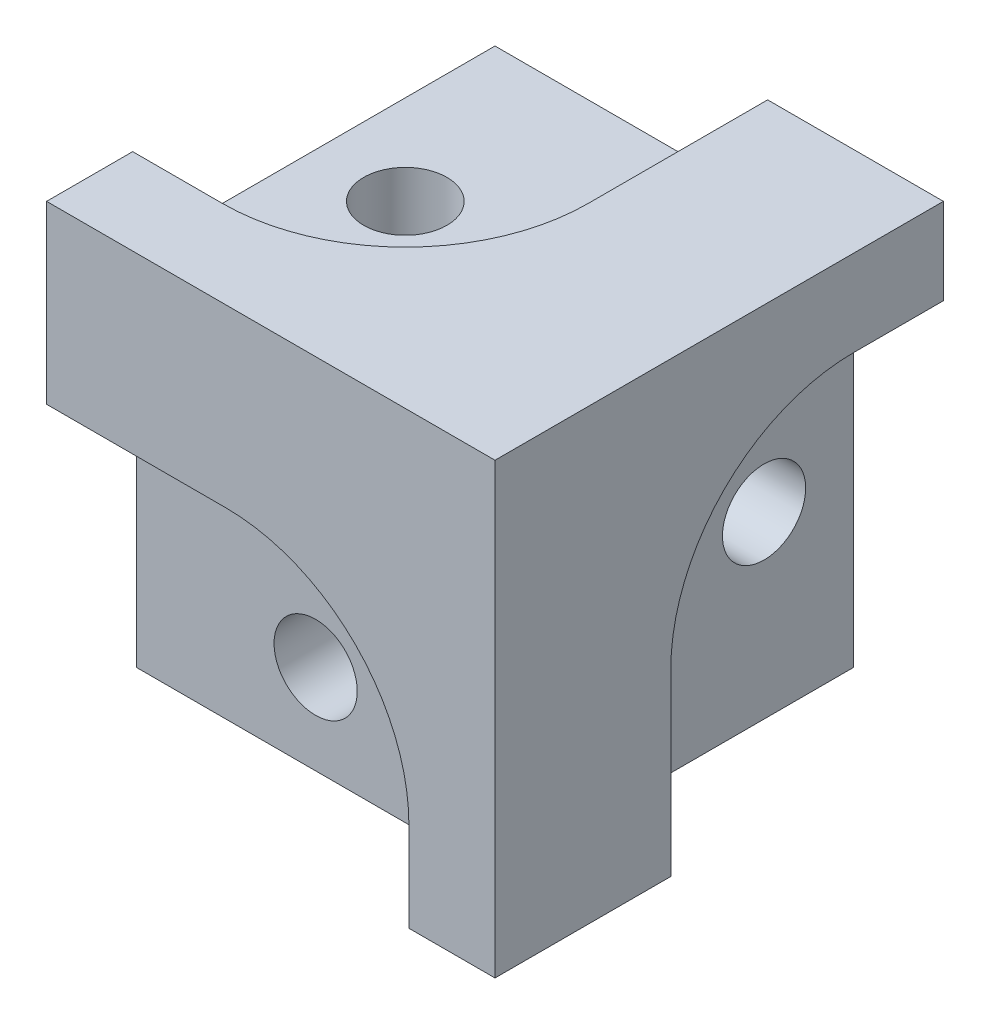
SolidWorks part; units mm, degrees
material "6061-T6 (SS)"
ref_plane "Front Plane" through (0, 0, 0) normal (0, 0, 1) x (1, 0, 0)
ref_plane "Top Plane" through (0, 0, 0) normal (0, 1, 0) x (1, 0, 0)
ref_plane "Right Plane" through (0, 0, 0) normal (1, 0, 0) x (0, 0, -1)
ref_axis "Axis1" [suppressed] through (0, 6.6, 0) along (0, -1, 0)
ref_axis "Axis2" [suppressed] through (0, 0, -6.6) along (0, 0, 1)
ref_plane "MIR-PLANE-1" through (0, 0, 0) normal (0, 0.7071, -0.7071) x (-1, 0, 0)
ref_plane "MIR-PLANE-2" through (0, 0, 0) normal (-0.7071, 0, 0.7071) x (0.7071, 0, 0.7071)
sketch "Sketch2" plane through (0, 0, 0) normal (0, 0, 1) x (1, 0, 0)
  line L1 (-7.9375, -7.9375) -> (7.9375, -7.9375)
  line L2 (-7.9375, -7.9375) -> (-7.9375, 7.9375)
  line L3 (-7.9375, 7.9375) -> (7.9375, 7.9375)
  line L4 (7.9375, -7.9375) -> (7.9375, 7.9375)
  line L5 (-7.9375, -7.9375) -> (7.9375, 7.9375) construction
  line L6 (-7.9375, 7.9375) -> (7.9375, -7.9375) construction
  point P0 (0, 0)
  dimension "D1" = 15.875
  dimension "D2" = 15.875
extrude "CUBE-BASE" add sketch "Sketch2" along normal blind 7.9375 and the other way blind 7.9375
hole_wizard "#4 Clearance Hole1" positions "Sketch3" profile "Sketch4" hole size "#4" standard "ANSI Inch" end condition through all
sketch "Sketch3" plane through (0, 0, 7.9375) normal (0, 0, 1) x (1, 0, 0)
  line L3 (7.9375, 7.9375) -> (-7.9375, 7.9375) construction
  line L4 (7.9375, -7.9375) -> (7.9375, 7.9375) construction
  point P6 (-1.5875, -4.7625)
  dimension "D1" = 9.525
  dimension "D2" = 12.7
sketch "Sketch4" plane through (-1.5875, -4.7625, 7.9375) normal (1, 0, 0) x (0, -1, 0)
  line L0 (0, 0) -> (0, 15.875)
  line L1 (0, 15.875) -> (1.4732, 15.875)
  line L2 (1.4732, 15.875) -> (1.4732, 0)
  line L5 (1.4732, 0) -> (0, 0)
  line L11 (0, -6.35) -> (0, 107.95) construction
  dimension "Thru Hole Dia." = 2.9464
  dimension "Thru Hole Depth" = 15.875
sketch "Sketch5" plane through (0, 0, 7.9375) normal (0, 0, 1) x (1, 0, 0)
  line L0 (-1.5875, 1.7145) -> (-7.9375, 1.7145)
  line L1 (-7.9375, -7.9375) -> (7.9375, -7.9375) construction
  line L2 (4.8895, -4.7625) -> (4.8895, -7.9375)
  line L4 (-7.9375, 7.9375) -> (-7.9375, -7.9375) construction
  line L5 (-7.9375, -7.9375) -> (4.8895, -7.9375)
  line L6 (-7.9375, 1.7145) -> (-7.9375, -7.9375)
  arc A0 (-1.5875, 1.7145) -> (4.8895, -4.7625) centre (-1.5875, -4.7625) cw
  circle A1 centre (-1.5875, -4.7625) radius 1.4732 construction
  circle A2 centre (-1.5875, -4.7625) radius 1.4732 construction
  point P11 (0, 0)
  dimension "D1" = 6.477
extrude "FRAME-RELIEF" cut sketch "Sketch5" against normal blind 3.175
mirror "Mirror1" [suppressed] about plane through (0, 0, 0) normal (0, 0.7071, -0.7071)
mirror "Mirror2" [suppressed] about plane through (0, 0, 0) normal (-0.7071, 0, 0.7071)
ref_axis "Axis3" through (7.9375, 7.9375, 7.9375) along (-0.5774, -0.5774, -0.5774)
pattern_circular "CirPattern1" count 3 over 360 about axis through (7.9375, 7.9375, 7.9375) along (-0.5774, -0.5774, -0.5774) of "FRAME-RELIEF", "#4 Clearance Hole1"
equation "\"D2@Sketch2\"=\"D1@Sketch2\""
equation "\"D1@CUBE-BASE\" = \"D1@Sketch2\" / 2"
equation "\"D2@CUBE-BASE\"=\"D1@Sketch2\"/2"
